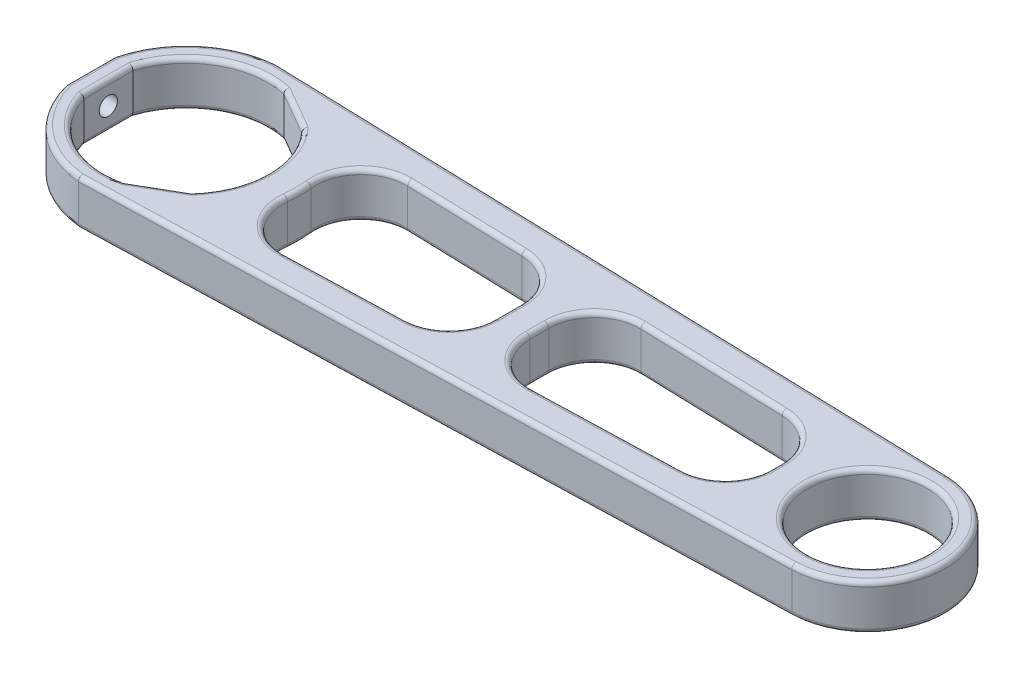
SolidWorks part; units mm, degrees
material "PA Type 6"
ref_plane "Plan de face" through (0, 0, 0) normal (0, 0, 1) x (1, 0, 0)
ref_plane "Plan de dessus" through (0, 0, 0) normal (0, 1, 0) x (1, 0, 0)
ref_plane "Plan de droite" through (0, 0, 0) normal (1, 0, 0) x (0, 0, -1)
sketch "Esquisse1" plane through (0, 0, 0) normal (0, 1, 0) x (1, 0, 0)
  line L8 (-38.1286, 10.8785) -> (38.1286, 8.5962)
  line L12 (-26.7981, 7.0378) -> (-1.75, 6.2881)
  line L16 (-45.7141, -2.7) -> (-45.7141, 2.7)
  line L17 (-35.1742, 8.7852) -> (-30.4976, 6.0852)
  line L18 (-30.4976, -6.0852) -> (-35.1742, -8.7852)
  line L22 (-47.7141, -2.7) -> (-47.7141, 2.7)
  line L28 (-28.1286, 0) -> (-24.6286, 0) construction
  line L30 (-38.1286, -10.8785) -> (38.1286, -8.5962)
  line L31 (-1.75, 6.2881) -> (-1.75, -6.2881)
  line L32 (-1.75, -6.2881) -> (-26.7981, -7.0378)
  line L33 (0, 9.7373) -> (0, -9.7373) construction
  line L34 (1.75, 6.1834) -> (1.75, -6.1834)
  line L35 (1.75, -6.1834) -> (29.31, -5.3585)
  line L36 (1.75, 6.1834) -> (29.31, 5.3585)
  line L37 (-1.75, 6.2881) -> (1.75, 6.1834) construction
  line L38 (27.7714, 0) -> (31.2714, 0) construction
  arc A4 (-38.1286, 10.8785) -> (-47.7141, 2.7) centre (-37.1286, 0) ccw
  arc A13 (-35.1742, 8.7852) -> (-45.7141, 2.7) centre (-37.1286, 0) ccw
  arc A14 (-45.7141, -2.7) -> (-35.1742, -8.7852) centre (-37.1286, 0) ccw
  arc A15 (-30.4976, -6.0852) -> (-30.4976, 6.0852) centre (-37.1286, 0) ccw
  arc A19 (-47.7141, -2.7) -> (-38.1286, -10.8785) centre (-37.1286, 0) ccw
  arc A20 (38.1286, -8.5962) -> (38.1286, 8.5962) centre (37.8714, 0) ccw
  circle A21 centre (37.8714, 0) radius 6.6
  arc A22 (-26.7981, -7.0378) -> (-26.7981, 7.0378) centre (-37.1286, 0) ccw
  arc A23 (29.31, -5.3585) -> (29.31, 5.3585) centre (37.8714, 0) cw
  point P8 (0, 0)
  point P16 (-45.7141, 0)
  point P18 (-47.7141, 0)
  point P21 (-37.1286, 0)
  point P24 (-37.1286, 0)
  point P35 (0, 6.2358)
  dimension "D5" = 18
  dimension "D2" = 8.6
  dimension "D4" = 13.2
  dimension "D6" = 5.4
  dimension "D8" = 5.4
  dimension "D11" = 3.5
  dimension "D13" = 75
  dimension "D10" = 1
  dimension "D14" = 3.5
  dimension "D17" = 3.5
  dimension "D15" = 3.5
  dimension "D9" = 2
  dimension "D7" = 3
extrude "Boss.-Extru.1" add sketch "Esquisse1" along normal blind 5
sketch "Esquisse2" plane through (-47.7141, 0, 0) normal (-1, 0, 0) x (0, 0, 1)
  line L0 (-2.7, 0) -> (2.7, 5) construction
  circle A0 centre (0, 2.5) radius 1
  dimension "D1" = 2
extrude "Enlèv. mat.-Extru.1" cut sketch "Esquisse2" against normal up to surface (2 mm away) up to face at (-45.7141, 2.5, 0)
fillet "Congé3" radius 5 8 edges at (29.31, 2.5, 5.3585) (29.31, 2.5, -5.3585) (-26.7981, 2.5, 7.0378) (-26.7981, 2.5, -7.0378) (1.75, 2.5, -6.1834) (1.75, 2.5, 6.1834) (-1.75, 2.5, -6.2881) (-1.75, 2.5, 6.2881)
fillet "Congé2" radius 0.5 58 edges at (37.8714, 0, 6.6) (-13.0874, 0, -6.6275) (-24.6286, 0, 0) (46.4714, 0, 0) (0, 0, -9.7373) (-44.2193, 0, -8.3105) (-47.7141, 0, 0) (-44.2193, 0, 8.3105) (0, 0, 9.7373) (-45.7141, 0, 0) (-41.6286, 0, -7.7942) (-32.8359, 0, -7.4352) (-28.1286, 0, 0) (-32.8359, 0, 7.4352) (-41.6286, 0, 7.7942) (-28.1286, 5, 0) (-32.8359, 5, -7.4352) (-41.6286, 5, -7.7942) (-45.7141, 5, 0) (-41.6286, 5, 7.7942) (-32.8359, 5, 7.4352) (37.8714, 5, 6.6) (-44.2193, 5, 8.3105) (-47.7141, 5, 0) (-44.2193, 5, -8.3105) (0, 5, -9.7373) (46.4714, 5, 0) (0, 5, 9.7373) (-13.0874, 5, -6.6275) (-24.6286, 5, 0) (-1.75, 0, 0) (-13.0874, 0, 6.6275) (14.9153, 0, 5.7893) (1.75, 0, 0) (14.9153, 0, -5.7893) (27.7714, 0, 0) (-1.75, 5, 0) (-13.0874, 5, 6.6275) (1.75, 5, 0) (14.9153, 5, 5.7893) (27.7714, 5, 0) (14.9153, 5, -5.7893) (-23.3887, 0, 5.2253) (-23.3887, 0, -5.2253) (3.2678, 0, 4.6195) (3.2678, 0, -4.6195) (26.4325, 0, -3.9678) (26.4325, 0, 3.9678) (-23.3887, 5, -5.2253) (-23.3887, 5, 5.2253) (3.2678, 5, -4.6195) (3.2678, 5, 4.6195) (26.4325, 5, 3.9678) (26.4325, 5, -3.9678) (-3.162, 0, -4.9178) (-3.162, 0, 4.9178) (-3.162, 5, 4.9178) (-3.162, 5, -4.9178)
equation "\"D2@Esquisse1\"=\"D4@Esquisse1\"/2 + 2"
